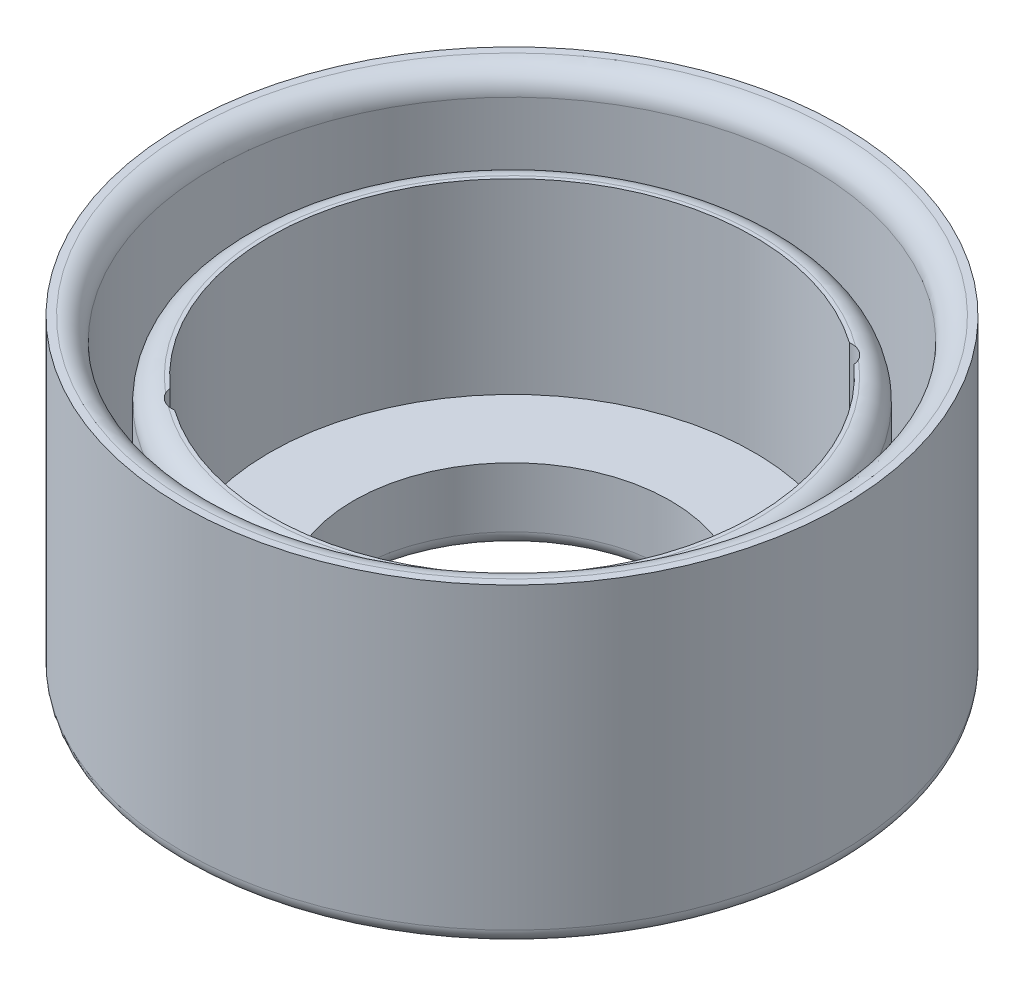
SolidWorks part; units mm, degrees
ref_plane "Alzado" through (0, 0, 0) normal (0, 0, 1) x (1, 0, 0)
ref_plane "Planta" through (0, 0, 0) normal (0, 1, 0) x (1, 0, 0)
ref_plane "Vista lateral" through (0, 0, 0) normal (1, 0, 0) x (0, 0, -1)
sketch "Croquis1" plane through (0, 0, 0) normal (0, 1, 0) x (1, 0, 0)
  circle A0 centre (0, 0) radius 17.95
  circle A1 centre (0, 0) radius 20.05
  circle A2 centre (0, 0) radius 22.05
  circle A3 centre (0, 0) radius 16.2
  dimension "D1" = 35.9
  dimension "D2" = 1.75
  dimension "D3" = 40.1
  dimension "D4" = 2
extrude "Saliente-Extruir1" add sketch "Croquis1" along normal blind 16 contours A2 A1 region at (-21.4263, 0, 0)
extrude "Saliente-Extruir2" add sketch "Croquis1<4>" along normal blind 12.5 separate body contours A0 A3 region at (-17.4423, 0, 0)
sketch "Croquis1<4>" plane through (0, 0, 0) normal (0, 1, 0) x (1, 0, 0) same geometry as "Croquis1"
extrude "Saliente-Extruir4" add sketch "Croquis1<6>" against normal blind 5 contours A3 | A0 A3 | A1 A0 | A2 A1 region at (-17.4423, 0, 0) region at (-19.4829, 0, 0) region at (-21.4263, 0, 0) region at (0, 0, 0)
sketch "Croquis1<6>" plane through (0, 0, 0) normal (0, 1, 0) x (1, 0, 0) same geometry as "Croquis1"
sketch "Croquis4" plane through (0, -5, 0) normal (0, -1, 0) x (1, 0, 0)
  line L0 (-9.5, 12) -> (0, 0) construction
  line L1 (0, 0) -> (9.5, -12) construction
  circle A0 centre (0, 0) radius 10.6
  circle A1 centre (-9.5, 12) radius 1.25
  circle A2 centre (9.5, -12) radius 1.25
  dimension "D1" = 21.2
  dimension "D4" = 2.5
  dimension "D2" = 19
  dimension "D3" = 24
extrude "Cortar-Extruir1" cut sketch "Croquis4" against normal up to next
fillet "Redondeo1" radius 1 1 edges at (0, -5, -10.6)
fillet "Redondeo2" radius 1.5 2 edges at (0, 12.5, 17.95) (0, 16, 20.05)
fillet "Redondeo3" radius 1 1 edges at (0, -5, 22.05)
